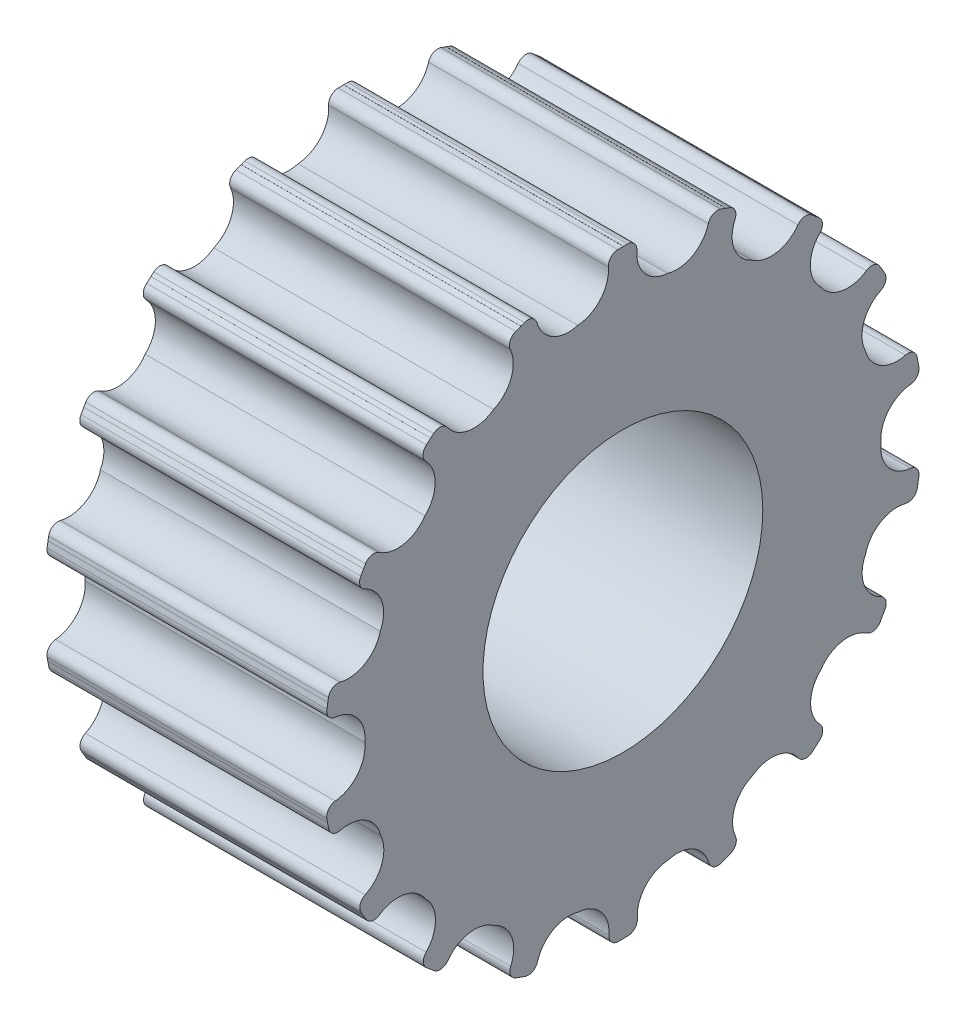
SolidWorks part; units mm, degrees
ref_plane "Front Plane" through (0, 0, 0) normal (0, 0, 1) x (1, 0, 0)
ref_plane "Top Plane" through (0, 0, 0) normal (0, 1, 0) x (1, 0, 0)
ref_plane "Right Plane" through (0, 0, 0) normal (1, 0, 0) x (0, 0, -1)
sketch "Sketch2" plane through (0, 0, 0) normal (1, 0, 0) x (0, 0, -1)
  circle A0 centre (0, -0.0658) radius 14.351
  dimension "D1" = 28.702
extrude "Boss-Extrude1" add sketch "Sketch2" along normal blind 12.7 contours A0
sketch "Sketch5" plane through (12.7, 0, 0) normal (1, 0, 0) x (0, 0, -1)
  line L0 (0, 0) -> (0, 13.5931) construction
  line L1 (0, 0) -> (2.7376, 15.5255) construction
  line L2 (-0.0495, 13.5423) -> (0.2045, 13.5423)
  line L3 (-0.0495, 13.5423) -> (-0.0495, 14.4123)
  line L4 (-0.0495, 14.4123) -> (2.5413, 14.4123)
  line L5 (4.9758, 13.5262) -> (2.5413, 14.4123)
  line L6 (4.6783, 12.7086) -> (4.9758, 13.5262)
  line L7 (4.6783, 12.7086) -> (4.4396, 12.7955)
  arc A0 (0.2045, 13.5423) -> (0.6331, 13.0785) centre (0.2045, 13.1123) cw
  arc A1 (0.6331, 13.0785) -> (2.0233, 11.4747) centre (2.1186, 12.9616) ccw
  arc A2 (3.8782, 12.5064) -> (2.0233, 11.4747) centre (2.4424, 12.9045) cw
  arc A3 (4.4396, 12.7955) -> (3.8782, 12.5064) centre (4.2925, 12.3915) ccw
  dimension "D3" = 0.43
  dimension "D4" = 1.49
  dimension "D1" = 10
  dimension "D2" = 0.254
  dimension "D5" = 0.87
  dimension "D6" = 2.9376
  dimension "D7" = 2.5908
extrude "Cut-Extrude2" cut sketch "Sketch5" against normal through all contours L5 L4 L3 L2 A0 A1 A2 A3 L7 L6
pattern_circular "CirPattern1" count 18 over 360 about axis through (12.7, -0.0658, 0) along (1, 0, 0) of "Cut-Extrude2"
sketch "Sketch6" plane through (12.7, 0, 0) normal (1, 0, 0) x (0, 0, -1)
  circle A0 centre (0, 0) radius 6.35
  dimension "D1" = 12.7
extrude "Cut-Extrude3" cut sketch "Sketch6" against normal through all both and the other way through all
equation "\"z\"= 18'INPUT: number of teeth"
equation "\"p\"= 5mm'INPUT: pitch (inches)"
equation "\"D_b\"= 1.25'INPUT: bore diameter (inches)"
equation "\"s\"= 0.5'INPUT: face width (inches)"
equation "\"D_p\"= \"z\" * \"p\" / pi'pitch circle diameter"
equation "\"theta\"= 180 / \"z\"'tooth angular size half (degrees)"
